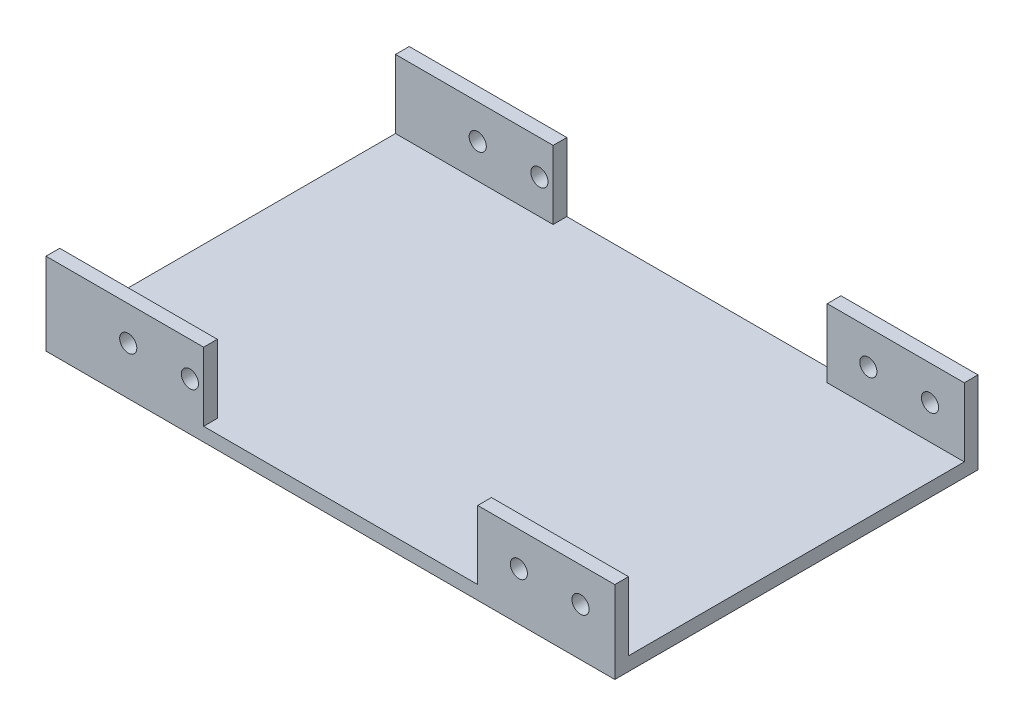
SolidWorks part; units mm, degrees
ref_plane "Front Plane" through (0, 0, 0) normal (0, 0, 1) x (1, 0, 0)
ref_plane "Top Plane" through (0, 0, 0) normal (0, 1, 0) x (1, 0, 0)
ref_plane "Right Plane" through (0, 0, 0) normal (1, 0, 0) x (0, 0, -1)
sketch "Sketch1" plane through (0, 0, 0) normal (0, 1, 0) x (1, 0, 0)
  line L1 (-61.9985, 27.694) -> (21.0015, 27.694)
  line L2 (-61.9985, 27.694) -> (-61.9985, -25.306)
  line L3 (-61.9985, -25.306) -> (21.0015, -25.306)
  line L4 (21.0015, 27.694) -> (21.0015, -25.306)
  dimension "D1" = 83
  dimension "D2" = 53
extrude "Boss-Extrude1" add sketch "Sketch1" along normal blind 2
sketch "Sketch2" plane through (0, 2, 0) normal (0, 1, 0) x (1, 0, 0)
  line L0 (21.0015, 27.694) -> (-61.9985, 27.694) construction
  line L1 (1.0015, 27.694) -> (21.0015, 27.694)
  line L2 (1.0015, 27.694) -> (1.0015, 25.694)
  line L3 (1.0015, 25.694) -> (21.0015, 25.694)
  line L4 (21.0015, 27.694) -> (21.0015, 25.694)
  line L5 (1.0015, -23.306) -> (21.0015, -23.306)
  line L6 (1.0015, -23.306) -> (1.0015, -25.306)
  line L7 (1.0015, -25.306) -> (21.0015, -25.306)
  line L8 (21.0015, -23.306) -> (21.0015, -25.306)
  line L9 (-61.9985, -25.306) -> (21.0015, -25.306) construction
  line L10 (21.0015, -25.306) -> (21.0015, 27.694) construction
  line L11 (-61.9985, 27.694) -> (-61.9985, -25.306) construction
  line L16 (-61.9985, 27.694) -> (-38.9985, 27.694)
  line L17 (-61.9985, 27.694) -> (-61.9985, 25.694)
  line L18 (-61.9985, 25.694) -> (-38.9985, 25.694)
  line L19 (-38.9985, 27.694) -> (-38.9985, 25.694)
  line L20 (-61.9985, -23.306) -> (-38.9985, -23.306)
  line L21 (-61.9985, -23.306) -> (-61.9985, -25.306)
  line L22 (-61.9985, -25.306) -> (-38.9985, -25.306)
  line L23 (-38.9985, -23.306) -> (-38.9985, -25.306)
  dimension "D1" = 20
  dimension "D2" = 2
  dimension "D3" = 20
  dimension "D4" = 2
  dimension "D5" = 0
  dimension "D6" = 0
  dimension "D7" = 0
  dimension "D8" = 0
  dimension "D9" = 2
  dimension "D10" = 2
  dimension "D11" = 60
  dimension "D12" = 60
  dimension "D13" = 0
  dimension "D14" = 0
  dimension "D15" = 0
  dimension "D16" = 0
extrude "Boss-Extrude2" add sketch "Sketch2" along normal blind 10
sketch "Sketch3" plane through (0, 0, 25.306) normal (0, 0, 1) x (1, 0, 0)
  line L1 (21.0015, 12) -> (21.0015, 0) construction
  line L2 (-38.9985, 2) -> (1.0015, 2) construction
  circle A0 centre (16.0015, 7) radius 1.25
  circle A1 centre (7.0015, 7) radius 1.25
  circle A2 centre (-40.9985, 7) radius 1.25
  circle A3 centre (-49.9985, 7) radius 1.25
  dimension "D1" = 2.5
  dimension "D2" = 2.5
  dimension "D3" = 2.5
  dimension "D4" = 2.5
  dimension "D5" = 5
  dimension "D6" = 5
  dimension "D7" = 9
  dimension "D8" = 5
  dimension "D9" = 5
  dimension "D10" = 5
  dimension "D11" = 9
  dimension "D12" = 48
extrude "Cut-Extrude1" cut sketch "Sketch3" against normal through all
